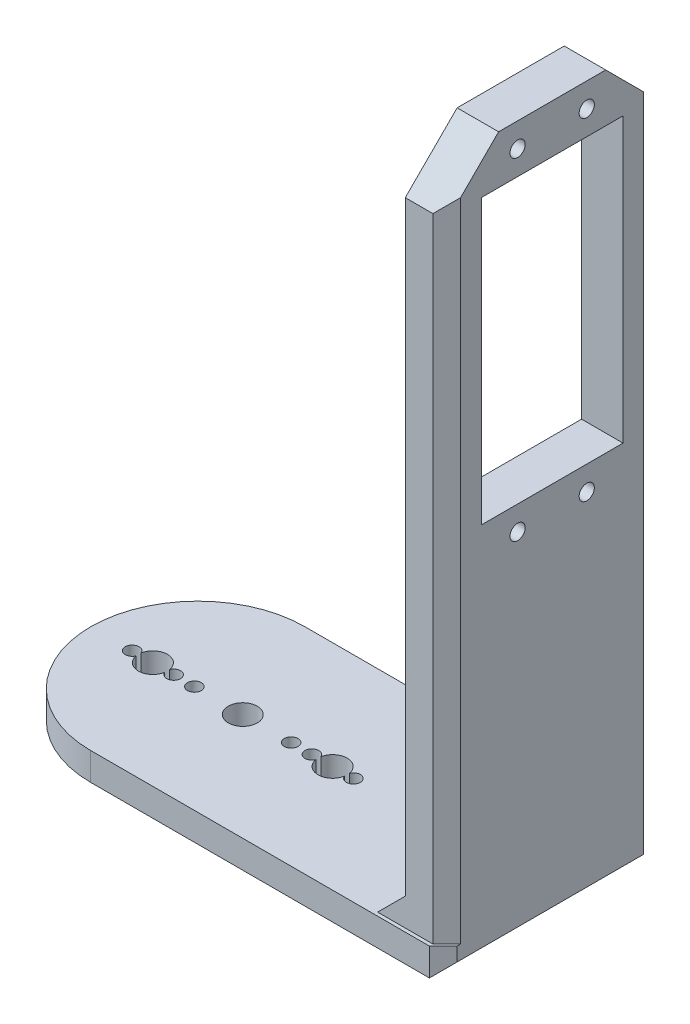
SolidWorks part; units mm, degrees
ref_plane "Alzado" through (0, 0, 0) normal (0, 0, 1) x (1, 0, 0)
ref_plane "Planta" through (0, 0, 0) normal (0, 1, 0) x (1, 0, 0)
ref_plane "Vista lateral" through (0, 0, 0) normal (1, 0, 0) x (0, 0, -1)
sketch "Croquis1" plane through (0, 0, 0) normal (0, 1, 0) x (1, 0, 0)
  line L0 (0, 0) -> (-7, 0) construction
  line L1 (-22, 15.5) -> (22, 15.5)
  line L2 (-22, 15.5) -> (-22, -15.5)
  line L3 (-22, -15.5) -> (22, -15.5)
  line L4 (22, 15.5) -> (22, -15.5)
  line L5 (-22, 15.5) -> (22, -15.5) construction
  line L6 (-22, -15.5) -> (22, 15.5) construction
  line L7 (0, 0) -> (7, 0) construction
  line L8 (-16, 0) -> (-13, 0) construction
  line L9 (-13, 0) -> (-10, 0) construction
  line L10 (-10, 0) -> (-7, 0) construction
  line L11 (0, 0) -> (0, -15.5) construction
  circle A0 centre (0, 0) radius 2.1
  circle A1 centre (7, 0) radius 1
  circle A2 centre (-7, 0) radius 1
  circle A3 centre (-10, 0) radius 1
  circle A4 centre (-13, 0) radius 1
  circle A5 centre (-16, 0) radius 1
  circle A6 centre (7, 0) radius 1
  circle A7 centre (10, 0) radius 1
  circle A8 centre (13, 0) radius 1
  circle A9 centre (16, 0) radius 1
  point P0 (0, 0)
  dimension "D1" = 4.2
  dimension "D4" = 2
  dimension "D2" = 44
  dimension "D3" = 31
  dimension "D5" = 7
  dimension "D6" = 4
  dimension "D7" = 3
extrude "Saliente-Extruir1" add sketch "Croquis1" along normal blind 6 contours L4 L1 L2 L3 A8 A0 A1 A2 A3 A4 A5 A7 A9
sketch "Croquis2" plane through (22, 0, 0) normal (1, 0, 0) x (0, 0, -1)
  line L1 (-15.5, 6) -> (15.5, 6)
  line L2 (-15.5, 6) -> (-15.5, 0)
  line L3 (-15.5, 0) -> (15.5, 0)
  line L4 (15.5, 6) -> (15.5, 0)
extrude "Saliente-Extruir2" add sketch "Croquis2" along normal blind 16.5
sketch "Croquis3" plane through (38.5, 0, 0) normal (1, 0, 0) x (0, 0, -1)
  line L0 (0.2582, 77.5) -> (15.5, 78) construction
  line L2 (15.5, 51) -> (15.5, 105)
  line L5 (15.5, 51) -> (15.5, 0)
  line L6 (0.2582, 77.5) -> (0.2582, 105) construction
  line L7 (15.5, 105) -> (-14.9918, 105)
  line L8 (15.5, 105) -> (15.5, 51)
  line L10 (-14.9918, 105) -> (-14.9918, 51)
  line L11 (0.2582, 51) -> (0.2582, 77.5) construction
  line L12 (0.2582, 77.5) -> (-14.9918, 77.5) construction
  line L13 (-14.9918, 51) -> (-14.9918, 0)
  line L15 (5.2582, 101.5) -> (-4.7418, 101.5) construction
  line L16 (5.2582, 101.5) -> (5.2582, 53.5) construction
  line L17 (5.2582, 53.5) -> (-4.7418, 53.5) construction
  line L18 (-4.7418, 101.5) -> (-4.7418, 53.5) construction
  line L19 (5.2582, 101.5) -> (-4.7418, 53.5) construction
  line L20 (5.2582, 53.5) -> (-4.7418, 101.5) construction
  line L21 (10.5082, 98) -> (-9.9918, 98)
  line L22 (10.5082, 98) -> (10.5082, 57)
  line L23 (10.5082, 57) -> (-9.9918, 57)
  line L24 (-9.9918, 98) -> (-9.9918, 57)
  line L25 (10.5082, 98) -> (-9.9918, 57) construction
  line L26 (10.5082, 57) -> (-9.9918, 98) construction
  line L29 (15.5, 51) -> (-14.9918, 51) construction
  line L31 (-14.9918, 105) -> (15.5, 105)
  line L32 (-14.9918, 105) -> (-14.9918, 51)
  line L34 (-15.5, 0) -> (15.5, 0) construction
  line L35 (15.5, 0) -> (15.5, 6) construction
  line L37 (15.5, 0) -> (-14.9918, 0)
  circle A0 centre (5.2582, 101.5) radius 1.1
  circle A1 centre (-4.7418, 101.5) radius 1.1
  circle A2 centre (-4.7418, 53.5) radius 1.1
  circle A3 centre (5.2582, 53.5) radius 1.1
  point P28 (0.2582, 57)
  dimension "D5" = 2.2
  dimension "D1" = 5
  dimension "D2" = 105
  dimension "D3" = 48
  dimension "D4" = 10
  dimension "D6" = 41
  dimension "D7" = 20.5
  dimension "D8" = 7
  dimension "D9" = 6
extrude "Saliente-Extruir3" add sketch "Croquis3" along normal blind 6
sketch "Croquis4" plane through (0, 0, 0) normal (0, -1, 0) x (1, 0, 0)
  circle A0 centre (0, 0) radius 1
  circle A1 centre (0, 0) radius 2.1
  circle A2 centre (0, 0) radius 2.1 construction
  dimension "D1" = 2
extrude "Saliente-Extruir4" add sketch "Croquis4" against normal blind 2
sketch "Croquis5" plane through (0, 6, 0) normal (0, 1, 0) x (1, 0, 0)
  circle A0 centre (-13, 0) radius 2.1
  circle A1 centre (13, 0) radius 2.1
  dimension "D1" = 4.2
extrude "Cortar-Extruir1" cut sketch "Croquis5" against normal blind 3.5
fillet "Redondeo1" radius 15.5 2 edges at (-22, 3, 15.5) (-22, 3, -15.5)
chamfer "Chaflán1" distance 2 angle 45 6 edges at (44.5, 55.5, 14.9918) (44.5, 52.5, -15.5) (19, 0, 15.5) (-17.4602, 0, 10.9602) (-17.4602, 0, -10.9602) (19, 0, -15.5)
chamfer "Chaflán2" distance 2 angle 45 1 edges at (44.5, 4, 15.5)
chamfer "Chaflán3" distance 4 angle 45 1 edges at (44.5, 0, 0)
chamfer "Chaflán4" distance 4 angle 45 1 edges at (38.5, 6, -0.2541)
chamfer "Chaflán5" distance 7.5 angle 45 3 edges at (40.5, 105, 14.9918) (43.5, 105, -14.5) (40.5, 105, -15.5)
